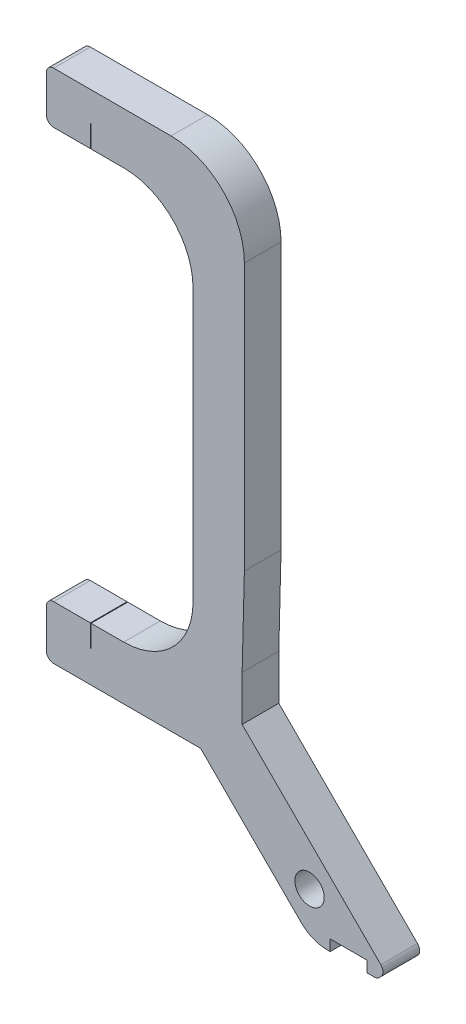
SolidWorks part; units mm, degrees
ref_plane "Front Plane" through (0, 0, 0) normal (0, 0, 1) x (1, 0, 0)
ref_plane "Top Plane" through (0, 0, 0) normal (0, 1, 0) x (1, 0, 0)
ref_plane "Right Plane" through (0, 0, 0) normal (1, 0, 0) x (0, 0, -1)
sketch "Sketch1" plane through (0, 0, 0) normal (0, 0, 1) x (1, 0, 0)
  line L0 (1, 0) -> (17, 0)
  line L1 (27, -10.1647) -> (27, -46.3772)
  line L2 (16.8019, -70.3054) -> (1, -70.3054)
  line L3 (0, -69.3054) -> (0, -64)
  line L4 (1, -63) -> (10.5397, -63)
  line L5 (20, -53.5397) -> (20, -16.4603)
  line L6 (10.5397, -7) -> (1, -7)
  line L7 (0, -6) -> (0, -1)
  line L14 (27, -10.1647) -> (27, -10)
  line L34 (16.8019, -70.3054) -> (26.6946, -70.3054) construction
  line L37 (26.6946, -58.4939) -> (27, -46.3772)
  line L42 (26.6946, -70.3054) -> (26.6946, -58.4939) construction
  line L43 (26.6946, -70.3054) -> (41.8593, -85.47) construction
  line L45 (34.738, -84.0056) -> (21.0378, -70.3054)
  line L48 (45.6077, -83.5615) -> (26.6946, -64.6485)
  line L49 (37.7477, -85.47) -> (26.6946, -68.5482) construction
  line L50 (24.9375, -70.3054) -> (46.3148, -84.2686) construction
  line L53 (16.8019, -70.3054) -> (21.0378, -70.3054)
  line L54 (26.6946, -58.4939) -> (26.6946, -64.3996)
  line L55 (26.6946, -64.3996) -> (26.6946, -64.6485)
  line L56 (44.6991, -85.47) -> (38.2735, -85.47)
  line L57 (45.4063, -85.1771) -> (45.6077, -84.9757)
  line L58 (43.4863, -87.0971) -> (46.4915, -90.1022) construction
  arc A2 (10.5397, -63) -> (20, -53.5397) centre (10.5397, -53.5397) ccw
  arc A3 (20, -16.4603) -> (10.5397, -7) centre (10.5397, -16.4603) ccw
  arc A4 (0, -64) -> (1, -63) centre (1, -64) cw
  arc A5 (0, -69.3054) -> (1, -70.3054) centre (1, -69.3054) ccw
  arc A6 (0, -1) -> (1, 0) centre (1, -1) cw
  arc A7 (0, -6) -> (1, -7) centre (1, -6) ccw
  arc A8 (17, 0) -> (27, -10) centre (17, -10) cw
  circle A10 centre (35.887, -79.4977) radius 2
  arc A11 (45.4063, -85.1771) -> (44.6991, -85.47) centre (44.6991, -84.47) cw
  arc A12 (45.6077, -84.9757) -> (45.6077, -83.5615) centre (44.9006, -84.2686) ccw
  arc A13 (38.2735, -85.47) -> (34.738, -84.0056) centre (38.2735, -80.47) cw
  point P11 (27, 0)
  point P25 (0, 0)
  point P30 (37.4955, 3.7564)
  point P31 (30.004, -73.6147)
  dimension "D8" = 1
  dimension "D6" = 10
  dimension "D7" = 4
  dimension "D9" = 1
  dimension "D10" = 5
  dimension "D1" = 7
  dimension "D2" = 7
  dimension "D4" = 20
  dimension "D3" = 135
  dimension "D5" = 13
extrude "Boss-Extrude1" add sketch "Sketch1" along normal blind 5
sketch "Sketch2" plane through (0, -63, 0) normal (0, 1, 0) x (1, 0, 0)
  line L0 (27, -2.5) -> (6.05, -2.5) construction
  line L1 (27, -5) -> (27, 0) construction
  line L2 (10.5397, 0) -> (1, 0) construction
  line L3 (6, -5) -> (6.1, -5)
  line L4 (6, -5) -> (6, 0)
  line L5 (6, 0) -> (6.1, 0)
  line L6 (6.1, -5) -> (6.1, 0)
  line L7 (6, -5) -> (6.1, 0) construction
  line L8 (6, 0) -> (6.1, -5) construction
  dimension "D2" = 0.1
extrude "Cut-Extrude1" cut sketch "Sketch2" against normal blind 3
sketch "Sketch3" plane through (0, -7, 0) normal (0, -1, 0) x (1, 0, 0)
  line L0 (27, 2.5) -> (6.05, 2.5) construction
  line L1 (27, 5) -> (27, 0) construction
  line L2 (1, 5) -> (10.5397, 5) construction
  line L3 (6, 0) -> (6.1, 0)
  line L4 (6, 0) -> (6, 5)
  line L5 (6, 5) -> (6.1, 5)
  line L6 (6.1, 0) -> (6.1, 5)
  line L7 (6, 0) -> (6.1, 5) construction
  line L8 (6, 5) -> (6.1, 0) construction
  dimension "D2" = 0.1
extrude "Cut-Extrude2" cut sketch "Sketch3" against normal blind 3
sketch "Sketch5" plane through (0, -85.47, 0) normal (0, -1, 0) x (1, 0, 0)
  line L0 (44.6991, 2.5) -> (38.2735, 2.5) construction
  line L1 (44.6991, 5) -> (44.6991, 0) construction
  line L2 (38.2735, 5) -> (38.2735, 0) construction
  line L4 (38.6991, 5) -> (38.6991, 0)
  line L5 (38.6991, 5) -> (43.6991, 5)
  line L6 (38.6991, 0) -> (43.6991, 0)
  line L7 (43.6991, 5) -> (43.6991, 0)
  line L8 (38.6991, 5) -> (43.6991, 0) construction
  line L9 (38.6991, 0) -> (43.6991, 5) construction
  point P9 (41.1991, 2.5)
  dimension "D1" = 3.5
  dimension "D2" = 5
extrude "Cut-Extrude3" cut sketch "Sketch5" against normal blind 1.5
equation "\"A.L\"= 0.07m"
equation "\"A.h\"= 0.007m"
equation "\"A.d\"= 0.005m"
equation "\"A.delta\"= 45.0001"
equation "\"A.w\"= 0m"
equation "\"A.v\"= 0.013m"
equation "\"A.s\"= 0.014m"
equation "\"A.t\"= 0.007m"
equation "\"B.L\"= 0.065m"
equation "\"B.h\"= 0.008m"
equation "\"B.s\"= 0.016m"
equation "\"B.t\"= 0.008m"
equation "\"C.h\"= 0.0065m"
equation "\"C.d\"= 0.005m"
equation "\"C.L\"= 0.05m"
equation "\"C.wmax\"= 0.003m"
equation "\"D.L\"= 0.06m"
equation "\"D.h\"= 0.008m"
equation "\"D.s\"= 0.012m"
equation "\"D.t\"= 0.008m"
equation "\"a_h\"= 0.0001m"
equation "\"a_d\"= 0.005m"
equation "\"a_L\"= 0.008m"
equation "\"b_h\"= 0.0004m"
equation "\"b_d\"= 0.005m"
equation "\"b_L\"= 0.007m"
equation "\"c_h\"= 0.0001m"
equation "\"c_d\"= 0.005m"
equation "\"c_L\"= 0.01m"
equation "\"d_h\"= 0.0001m"
equation "\"d_d\"= 0.005m"
equation "\"d_L\"= 0.01m"
equation "\"S.h\"= 0.015m"
equation "\"S.L\"= 0.09275m"
equation "\"D1@Sketch1\"=\"A.h\""
equation "\"D2@Sketch1\"=\"A.t\""
equation "\"D4@Sketch1\"=\"A.s\"+0.006"
equation "\"D1@Boss-Extrude1\"=\"A.d\""
equation "\"D1@Sketch2\"=\"A.h\"+\"A.s\"-\"a_h\"/2"
equation "\"D2@Sketch2\"=\"d_h\""
equation "\"D1@Sketch3\"=\"A.h\"+\"A.s\"-\"d_h\"/2"
equation "\"D2@Sketch3\"=\"d_h\""
equation "\"D5@Sketch1\"=0.013m"
